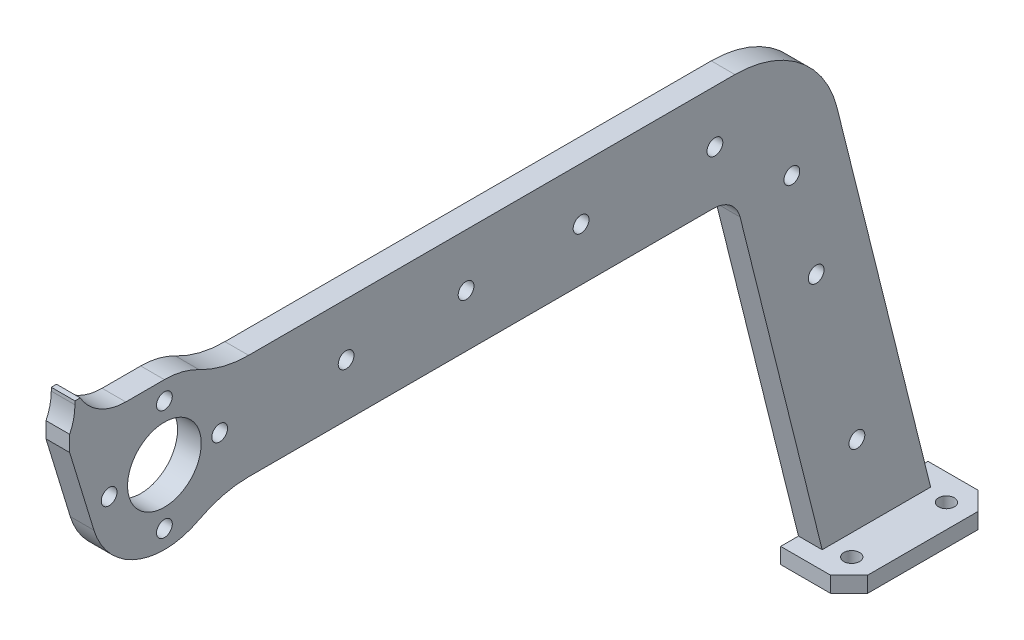
SolidWorks part; units mm, degrees
ref_plane "前视基准面" through (0, 0, 0) normal (0, 0, 1) x (1, 0, 0)
ref_plane "上视基准面" through (0, 0, 0) normal (0, 1, 0) x (1, 0, 0)
ref_plane "右视基准面" through (0, 0, 0) normal (1, 0, 0) x (0, 0, -1)
sketch "草图1" plane through (0, 0, 0) normal (1, 0, 0) x (0, 0, -1)
  line L2 (109.4025, -13.942) -> (125, -76.5)
  line L3 (125, -76.5) -> (145.6123, -76.5)
  line L4 (145.6123, -76.5) -> (127.8256, -5.1616)
  line L5 (108.4197, 10) -> (16, 10)
  line L7 (16, -10) -> (104.357, -10)
  line L8 (135.6657, -77.942) -> (114.3213, 7.6656) construction
  line L9 (0, 14) -> (-18, 14)
  line L10 (-18, 14) -> (-18, 11)
  line L11 (-18, 11) -> (-13.3889, -4.091)
  line L12 (104.357, -15.2) -> (104.357, -10) construction
  arc A0 (6.5882, 12.3529) -> (6.5882, -12.3529) centre (0, 0) ccw
  circle A1 centre (0, 0) radius 10.5 construction
  circle A2 centre (0, 0) radius 7
  circle A3 centre (0, 10.5) radius 1.5
  arc A7 (127.8256, -5.1616) -> (108.4197, 10) centre (108.4197, -10) ccw
  arc A8 (104.357, -10) -> (109.4025, -13.942) centre (104.357, -15.2) cw
  arc A15 (16, 10) -> (6.5882, 12.3529) centre (16, 30) cw
  arc A16 (16, -10) -> (6.5882, -12.3529) centre (16, -30) ccw
  circle A17 centre (10.5, 0) radius 1.5
  circle A18 centre (0, -10.5) radius 1.5
  circle A19 centre (-10.5, 0) radius 1.5
  point P25 (0, 0)
  point P36 (135.3061, -76.5)
  point P43 (9.798, 7.7889)
  point P50 (9.798, -10)
  dimension "D1" = 28
  dimension "D3" = 14
  dimension "D4" = 3
  dimension "D9" = 20
  dimension "D13" = 4
  dimension "D24" = 20
  dimension "D25" = 20
  dimension "D5" = 21
  dimension "D6" = 104
  dimension "D7" = 20
  dimension "D8" = 125
  dimension "D10" = 76.5
  dimension "D11" = 20
  dimension "D12" = 20.6123
  dimension "D14" = 5.2
  dimension "D21" = 18
  dimension "D22" = 3
  dimension "D15" = 88.357
extrude "凸台-拉伸1" add sketch "草图1" along normal mid plane 4.5 contours A16 L7 A8 L2 L3 L4 A7 L5 A15 A0 A18 A17 A3 A2 | A0 L9 L10 L11 | A16 A0 region at (0, -9.6565, -108.6881) region at (0, 9.7023, 13.097)
sketch "草图5" plane through (0, -76.5, 0) normal (0, -1, 0) x (1, 0, 0)
  line L0 (-2.25, -109.4025) -> (-2.25, -125) construction
  line L1 (-2.25, -121.6123) -> (10.75, -121.6123)
  line L2 (-2.25, -121.6123) -> (-2.25, -149.6123)
  line L3 (-2.25, -149.6123) -> (10.75, -149.6123)
  line L4 (10.75, -121.6123) -> (10.75, -149.6123)
  line L5 (2.25, -145.6123) -> (-2.25, -145.6123) construction
  dimension "D1" = 13
  dimension "D2" = 28
  dimension "D3" = 4
extrude "凸台-拉伸3" add sketch "草图5" along normal blind 3
sketch "草图6" plane through (0, -76.5, 0) normal (0, 1, 0) x (1, 0, 0)
  line L0 (10.75, 135.6123) -> (-2.25, 135.6123) construction
  line L1 (10.75, 149.6123) -> (10.75, 121.6123) construction
  line L2 (-2.25, 145.6123) -> (-2.25, 127.8256) construction
  line L5 (2.25, 145.6123) -> (2.25, 127.8256) construction
  circle A0 centre (6.25, 144.6123) radius 1.5
  circle A1 centre (6.25, 126.6123) radius 1.5
  dimension "D3" = 3
  dimension "D1" = 9
  dimension "D2" = 4
extrude "切除-拉伸2" cut sketch "草图6" against normal through all
sketch "草图7" plane through (2.25, 0, 0) normal (1, 0, 0) x (0, 0, -1)
  line L1 (0, 14) -> (-18, 14) construction
  line L2 (-17.0011, 14) -> (-17.0011, 18.9987)
  line L3 (-17.0011, 18.9987) -> (-16.0023, 18.9987)
  line L4 (-16.0023, 18.9987) -> (-16.0023, 14)
  line L5 (-16.0023, 14) -> (-17.0011, 14)
extrude "凸台-拉伸4" add sketch "草图7" against normal up to vertex (4.5 mm away) up to point (-2.25, 14, 0)
fillet "圆角1" radius 10 2 edges at (0, 14, 16.0023) (0, 14, 17.0011)
chamfer "倒角1" distance 3.5 angle 45 2 edges at (10.75, -78, -121.6123) (10.75, -78, -149.6123)
sketch "草图8" plane through (-2.25, 0, 0) normal (-1, 0, 0) x (0, 0, 1)
  line L0 (-16, 10) -> (-16, -10) construction
  line L1 (-108.4197, 10) -> (-104.357, -10) construction
  line L2 (-127.8256, -5.1616) -> (-109.4025, -13.942) construction
  line L3 (-122.5808, -66.797) -> (-141.9867, -61.9586) construction
  line L4 (-109.4025, -13.942) -> (-125, -76.5) construction
  line L5 (-145.6123, -76.5) -> (-127.8256, -5.1616) construction
  line L6 (-132.2837, -64.3778) -> (-118.6141, -9.5518)
  line L7 (-106.3883, 0) -> (-16, 0)
  arc A0 (-104.357, -10) -> (-109.4025, -13.942) centre (-104.357, -15.2) ccw construction
  arc A1 (-118.6141, -9.5518) -> (-106.3883, 0) centre (-106.3883, -12.6) cw
  dimension "D1" = 10
sketch "草图9" plane through (-2.25, 0, 0) normal (-1, 0, 0) x (0, 0, 1)
  line L0 (-132.2837, -64.3778) -> (-118.6141, -9.5518) construction
  line L1 (-106.3883, 0) -> (-16, 0) construction
  point P0 (-131.6026, -61.6459)
  point P1 (-123.8611, -30.5965)
  point P4 (-104.6157, 0)
  point P5 (-79.1822, 0)
  point P8 (-57.3282, 0)
  point P9 (-34.5323, 0)
  point P10 (-130.4952, -57.2044)
  point P11 (-119.2336, -12.0366)
  point P12 (-123.8611, -30.5965)
  dimension "D1" = 32
sketch "草图10" plane through (-2.25, 0, 0) normal (-1, 0, 0) x (0, 0, 1)
  circle A0 centre (-34.5323, 0) radius 1.5
  dimension "D1" = 3
extrude "切除-拉伸3" cut sketch "草图10" against normal blind 10
pattern_sketch "草图阵列1" of "切除-拉伸3" driven by "草图9"
